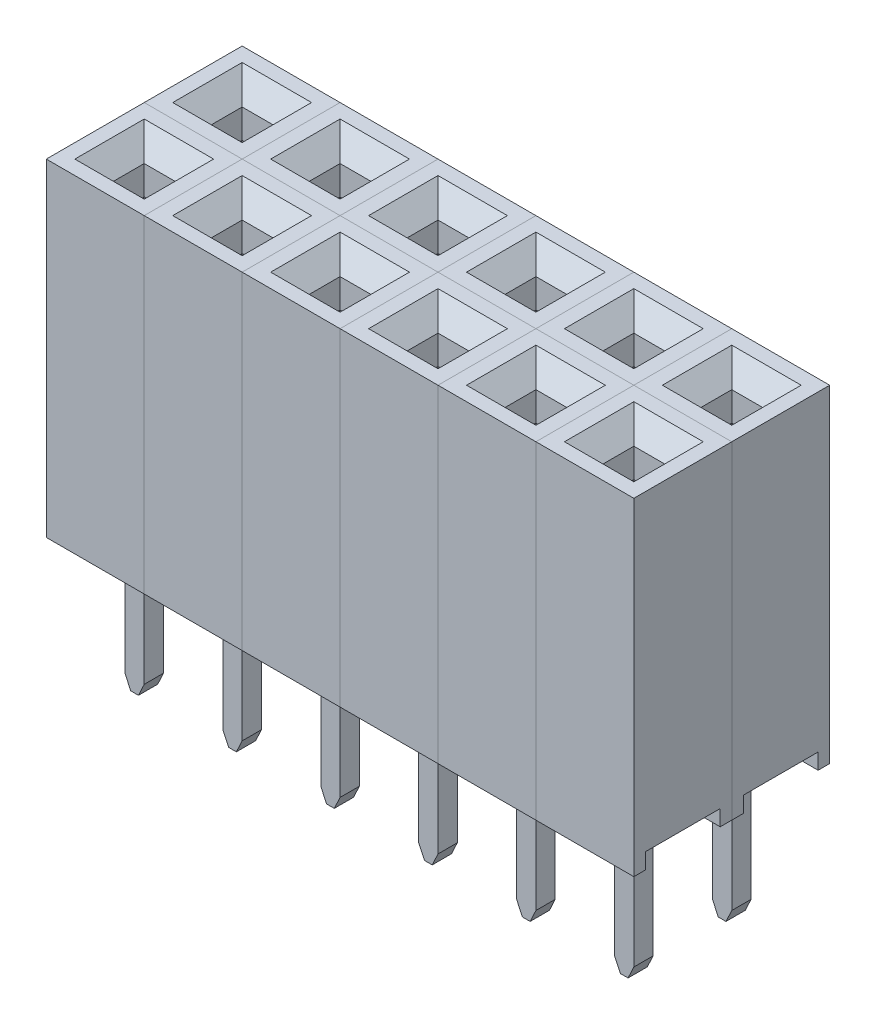
SolidWorks part; units mm, degrees
note: The reader was unsure of these and kept them because the rebuilt part matched: shared geometry of "Sketch9<3>".
ref_plane "Front" through (0, 0, 0) normal (0, 0, 1) x (1, 0, 0)
ref_plane "Top" through (0, 0, 0) normal (0, 1, 0) x (1, 0, 0)
ref_plane "Right" through (0, 0, 0) normal (1, 0, 0) x (0, 0, -1)
sketch "Sketch1" plane through (0, 0, 0) normal (0, 0, 1) x (1, 0, 0)
  line L1 (1.27, -4.25) -> (-1.27, -4.25)
  line L2 (1.27, -4.25) -> (1.27, 4.25)
  line L3 (1.27, 4.25) -> (-1.27, 4.25)
  line L4 (-1.27, -4.25) -> (-1.27, 4.25)
  line L5 (1.27, -4.25) -> (-1.27, 4.25) construction
  line L6 (1.27, 4.25) -> (-1.27, -4.25) construction
  point P0 (0, 0)
  dimension "D1" = 2.54
  dimension "D2" = 8.5
extrude "Boss-Extrude1" add sketch "Sketch1" along normal mid plane 2.54
sketch "Sketch2" plane through (0, 0, 0) normal (1, 0, 0) x (0, 0, -1)
  line L0 (-0.97, -4.25) -> (0.97, -4.25)
  line L1 (-1.27, -4.25) -> (1.27, -4.25) construction
  line L2 (0.97, -4.25) -> (0.97, -3.8396)
  line L3 (0.97, -3.8396) -> (-0.97, -3.8396)
  line L4 (-0.97, -3.8396) -> (-0.97, -4.25)
  line L5 (1.27, -4.25) -> (1.27, 4.25) construction
  line L6 (-1.27, -4.25) -> (-1.27, 4.25) construction
  dimension "D1" = 0.3
  dimension "D2" = 0.3
extrude "Cut-Extrude1" cut sketch "Sketch2" against normal mid plane 100
sketch "Sketch4" plane through (0, 4.25, 0) normal (0, 1, 0) x (1, 0, 0)
  line L0 (-1.27, 0) -> (1.27, 0) construction
  line L1 (-1.27, -1.27) -> (-1.27, 1.27) construction
  line L2 (1.27, -1.27) -> (1.27, 1.27) construction
  line L4 (-0.875, 0.875) -> (0.875, 0.875)
  line L5 (-0.875, 0.875) -> (-0.875, -0.875)
  line L6 (-0.875, -0.875) -> (0.875, -0.875)
  line L7 (0.875, 0.875) -> (0.875, -0.875)
  line L8 (-0.875, 0.875) -> (0.875, -0.875) construction
  line L9 (-0.875, -0.875) -> (0.875, 0.875) construction
  line L10 (-0.4, 0.4) -> (0.4, 0.4)
  line L11 (-0.4, 0.4) -> (-0.4, -0.4)
  line L12 (-0.4, -0.4) -> (0.4, -0.4)
  line L13 (0.4, 0.4) -> (0.4, -0.4)
  line L14 (-0.4, 0.4) -> (0.4, -0.4) construction
  line L15 (-0.4, -0.4) -> (0.4, 0.4) construction
  point P6 (0, 0)
  point P11 (0, 0)
  point P16 (0, 0)
  dimension "D1" = 1.75
  dimension "D2" = 0.8
extrude "Cut-Extrude2" cut sketch "Sketch4" against normal blind 1.5 contours L13 L10 L11 L12
chamfer "Chamfer1" distance 0.5 angle 45 4 edges at (0, 4.25, -0.4) (-0.4, 4.25, 0) (0, 4.25, 0.4) (0.4, 4.25, 0)
sketch "Sketch5" plane through (0, 0, 0) normal (0, 1, 0) x (1, 0, 0)
  line L1 (-0.9, 0.9) -> (0.9, 0.9)
  line L2 (-0.9, 0.9) -> (-0.9, -0.9)
  line L3 (-0.9, -0.9) -> (0.9, -0.9)
  line L4 (0.9, 0.9) -> (0.9, -0.9)
extrude "Cut-Extrude3" cut sketch "Sketch5" against normal blind 3 and the other way blind 3
sketch "Sketch9" plane through (0, 0, 0) normal (0, 0, 1) x (1, 0, 0)
  line L0 (0, 1.6008) -> (0, -6.2684) construction
  line L1 (0.8528, -1.3416) -> (0.6022, -1.2609)
  line L2 (0.6022, -1.2609) -> (0.4133, 1.4919)
  line L3 (0.2803, 1.3393) -> (0.5075, -1.9717)
  line L4 (0.8528, -1.3416) -> (0.8528, -2.6933)
  line L5 (0.8528, -2.6933) -> (0.2807, -3.0533)
  line L6 (0.2807, -3.0533) -> (-0.2807, -3.0533)
  line L7 (-0.8528, -2.6933) -> (-0.2807, -3.0533)
  line L8 (-0.8528, -1.3416) -> (-0.8528, -2.6933)
  line L9 (-0.8528, -1.3416) -> (-0.6022, -1.2609)
  line L10 (-0.6022, -1.2609) -> (-0.4133, 1.4919)
  line L11 (-0.2803, 1.3393) -> (-0.5075, -1.9717)
  line L12 (-0.1, -7.6212) -> (0.1, -7.6212)
  line L13 (0.1, -7.6212) -> (0.25, -7.2995)
  line L14 (0.25, -7.2995) -> (0.25, -3.0533)
  line L15 (-0.1, -7.6212) -> (-0.25, -7.2995)
  line L16 (-0.25, -7.2995) -> (-0.25, -3.0533)
  line L19 (0, 0) -> (0, -10.2857) construction
  arc A0 (0.4133, 1.4919) -> (0.2803, 1.3393) centre (0.2705, 1.4821) ccw
  arc A1 (0.5075, -1.9717) -> (0, -2.3943) centre (0.101, -1.9996) cw
  arc A2 (-0.5075, -1.9717) -> (0, -2.3943) centre (-0.101, -1.9996) ccw
  arc A3 (-0.4133, 1.4919) -> (-0.2803, 1.3393) centre (-0.2705, 1.4821) cw
  point P16 (0, -3.0533)
  point P24 (-0.25, -4.3212)
  dimension "D1" = 115
  dimension "D2" = 115
  dimension "D3" = 0.25
  dimension "D4" = 0.2
  dimension "D5" = 0.25
  dimension "D6" = 3.3
extrude "Boss-Extrude4" add sketch "Sketch9" along normal mid plane 1.7 contours A1 L0 L6 L5 L4 L1 L2 A0 L3 | L0 A2 L11 A3 L10 L9 L8 L7 L6 | L14 L13 L12 L15 L16
extrude "Boss-Extrude5" add sketch "Sketch9<3>" along normal mid plane 0.5
sketch "Sketch9<3>" plane through (0, 0, 0) normal (0, 0, 1) x (1, 0, 0) same geometry as "Sketch9"
pattern_linear "LPattern1" count 6 spacing 2.54 along (-1, 0, 0) count 2 spacing 2.54 along (0, 0, -1) of bodies 108
